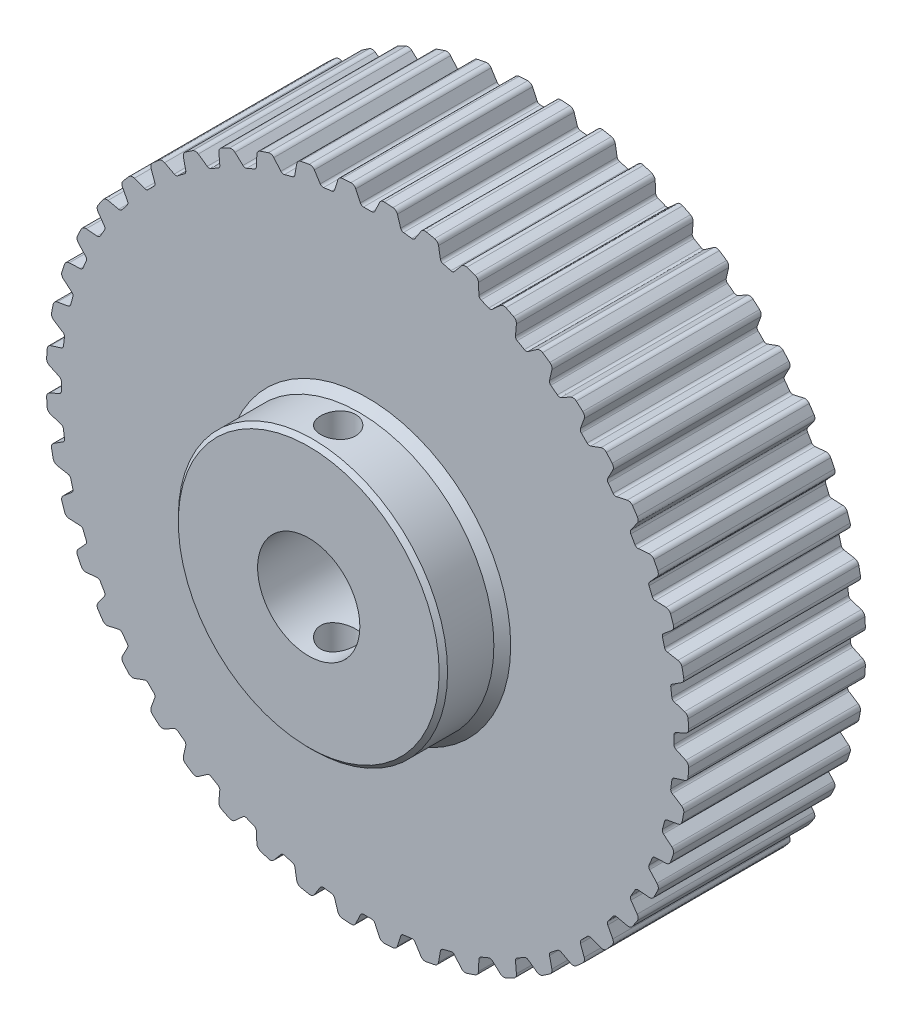
SolidWorks part; units mm, degrees
material "ABS"
ref_plane "Front Plane" through (0, 0, 0) normal (0, 0, 1) x (1, 0, 0)
ref_plane "Top Plane" through (0, 0, 0) normal (0, 1, 0) x (1, 0, 0)
ref_plane "Right Plane" through (0, 0, 0) normal (1, 0, 0) x (0, 0, -1)
sketch "Sketch1" plane through (0, 0, 0) normal (0, 0, 1) x (1, 0, 0)
  circle A0 centre (0, 0) radius 38.1972
  dimension "D1" = 76.3944
extrude "Boss-Extrude1" add sketch "Sketch1" along normal blind 21
sketch "Sketch2" plane through (0, 0, 21) normal (0, 0, 1) x (1, 0, 0)
  circle A0 centre (0, 0) radius 16
  dimension "D1" = 32
extrude "Boss-Extrude2" add sketch "Sketch2" along normal blind 7
sketch "Sketch3" plane through (0, 0, 28) normal (0, 0, 1) x (1, 0, 0)
  circle A0 centre (0, 0) radius 6.075
  dimension "D1" = 12.15
extrude "Cut-Extrude1" cut sketch "Sketch3" against normal through all
sketch "Sketch4" plane through (0, 0, 21) normal (0, 0, 1) x (1, 0, 0)
  line L1 (-1.593, 38.1972) -> (-0.75, 36.3895)
  line L2 (1.593, 38.1972) -> (0.75, 36.3895)
  line L3 (0, -44.7868) -> (0, 44.7868) construction
  line L4 (-1.593, 38.1972) -> (1.593, 38.1972)
  circle A0 centre (0, 0) radius 36.3972 construction
  circle A1 centre (0, 0) radius 38.1972 construction
  arc A2 (-0.75, 36.3895) -> (0.75, 36.3895) centre (0, 0) cw
  circle A3 centre (0, 0) radius 38.1972 construction
  point P11 (0, 36.3972)
  dimension "D1" = 1.8
  dimension "D2" = 25
  dimension "D4" = 1.5
  dimension "D3" = 25
extrude "Cut-Extrude2" cut sketch "Sketch4" against normal through all
fillet "Fillet1" radius 0.4 2 edges at (0.75, 36.3895, 10.5) (-0.75, 36.3895, 10.5)
fillet "Fillet2" radius 0.6 2 edges at (1.5778, 38.1646, 10.5) (-1.5778, 38.1646, 10.5)
ref_axis "Axis1" through (0, 0, 0) along (0, 0, 1)
pattern_circular "CirPattern1" count 48 over 360 about axis through (0, 0, 0) along (0, 0, 1) of "Cut-Extrude2", "Fillet1", "Fillet2"
sketch "Sketch5" plane through (0, 0, 21) normal (0, 0, 1) x (1, 0, 0)
  line L0 (0, -44.7868) -> (0, 44.7868) construction
  circle A0 centre (0, 26) radius 6
  circle A1 centre (0, 0) radius 26 construction
  dimension "D1" = 52
  dimension "D2" = 12
extrude "Cut-Extrude3" [suppressed] cut sketch "Sketch5" against normal through all
pattern_circular "CirPattern2" [suppressed] count 8 over 360 about axis through (0, 0, 0) along (0, 0, 1) of bodies 113
sketch "Sketch6" plane through (0, 0, 0) normal (0, 1, 0) x (1, 0, 0)
  line L0 (0, -44.7868) -> (0, 44.7868) construction
  line L1 (0, -21) -> (0, -28) construction
  line L2 (-0.4918, -21) -> (0.4918, -21) construction
  line L3 (-16, -28) -> (16, -28) construction
  circle A0 centre (0, -24.5) radius 2.075
  point P11 (0, -24.5)
  dimension "D1" = 4.15
extrude "Cut-Extrude4" cut sketch "Sketch6" against normal mid plane 50
chamfer "Chamfer1" distance 0.5 angle 45 1 edges at (16, 0, 28)
chamfer "Chamfer2" distance 1 angle 45 1 edges at (16, 0, 21)
